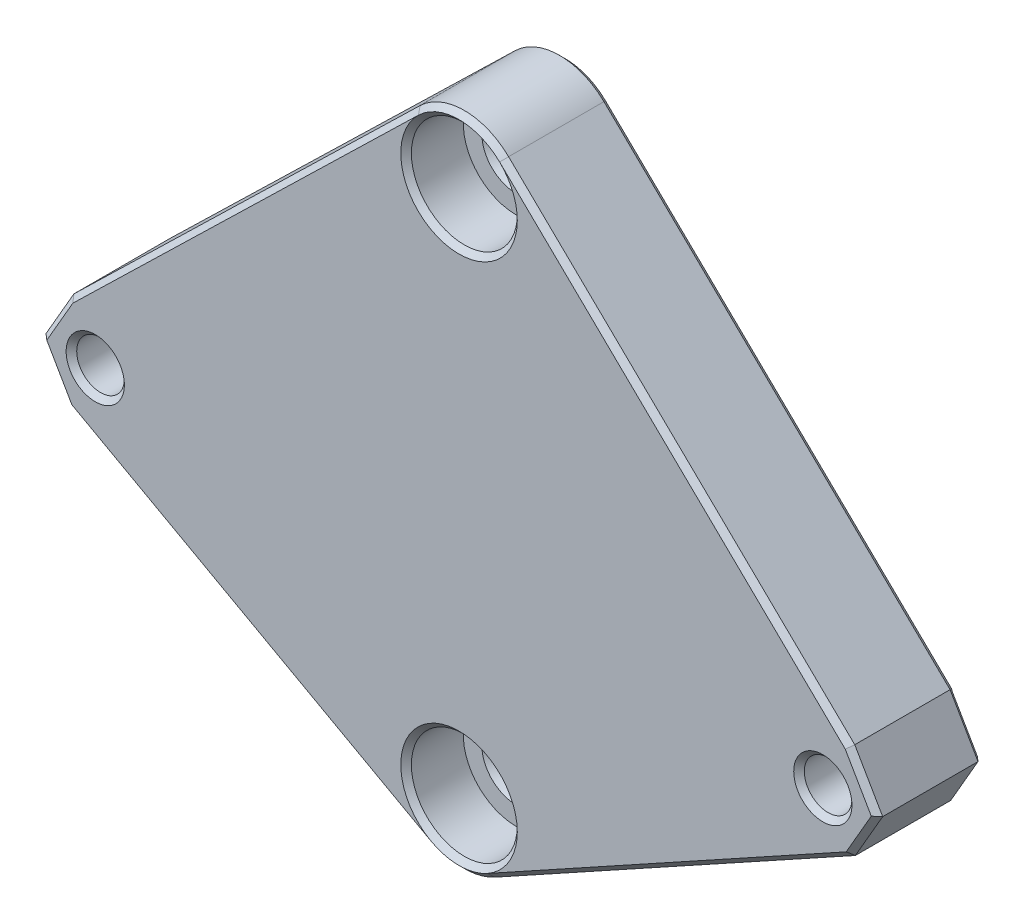
SolidWorks part; units mm, degrees
ref_plane "Top" through (0, 0, 0) normal (0, 0, 1) x (1, 0, 0)
ref_plane "Front" through (0, 0, 0) normal (0, 1, 0) x (1, 0, 0)
ref_plane "Right" through (0, 0, 0) normal (1, 0, 0) x (0, 0, -1)
sketch "Sketch1" plane through (0, 0, 0) normal (0, 0, 1) x (1, 0, 0)
  line L1 (0, 0) -> (79, 0)
  line L2 (0, 0) -> (0, 70)
  line L3 (0, 70) -> (79, 70)
  line L4 (79, 0) -> (79, 70)
  dimension "D1" = 79
  dimension "D2" = 70
extrude "Boss-Extrude1" add sketch "Sketch1" along normal blind 10
sketch "Sketch4" plane through (0, 0, 10) normal (0, 0, 1) x (1, 0, 0)
  line L0 (5.15, 28) -> (73.85, 28)
  line L2 (79, 0) -> (79, 70) construction
  line L5 (79, 70) -> (0, 70) construction
  point P2 (39.5, 28)
  dimension "D1" = 68.7
  dimension "D2" = 39.5
  dimension "D3" = 42
hole_wizard "M4 Clearance Hole1" positions "Sketch5" profile "Sketch6" hole size "M4" standard "DIN" end condition through all
sketch "Sketch5" plane through (0, 0, 10) normal (0, 0, 1) x (1, 0, 0)
  point P0 (5.15, 28)
  point P3 (73.85, 28)
sketch "Sketch6" plane through (5.15, 28, 10) normal (1, 0, 0) x (0, -1, 0)
  line L0 (0, 0) -> (0, 10)
  line L1 (0, 10) -> (2.25, 10)
  line L2 (2.25, 10) -> (2.25, 0)
  line L5 (2.25, 0) -> (0, 0)
  line L11 (0, -6.35) -> (0, 107.95) construction
  dimension "Thru Hole Dia." = 4.5
  dimension "Thru Hole Depth" = 10
sketch "Sketch11" plane through (0, 0, 0) normal (0, 0, -1) x (-1, 0, 0)
  line L0 (-79, 70) -> (0, 70) construction
  line L1 (-69.6353, 28) -> (-71.7427, 31.65)
  line L2 (-71.7427, 31.65) -> (-75.9573, 31.65)
  line L3 (-75.9573, 31.65) -> (-78.0647, 28)
  line L4 (-78.0647, 28) -> (-75.9573, 24.35)
  line L5 (-75.9573, 24.35) -> (-71.7427, 24.35)
  line L6 (-71.7427, 24.35) -> (-69.6353, 28)
  line L7 (-9.3647, 28) -> (-7.2573, 24.35)
  line L8 (-7.2573, 24.35) -> (-3.0427, 24.35)
  line L9 (-3.0427, 24.35) -> (-0.9353, 28)
  line L10 (-0.9353, 28) -> (-3.0427, 31.65)
  line L11 (-3.0427, 31.65) -> (-7.2573, 31.65)
  line L12 (-7.2573, 31.65) -> (-9.3647, 28)
  circle A0 centre (-73.85, 28) radius 3.65 construction
  circle A1 centre (-5.15, 28) radius 3.65 construction
  dimension "D1" = 7.3
  dimension "D2" = 7.3
extrude "Cut-Extrude3" cut sketch "Sketch11" against normal blind 3.5
sketch "Sketch12" plane through (0, 0, 10) normal (0, 0, -1) x (-1, 0, 0)
  line L0 (-39.5, 60) -> (-39.5, 10)
  line L1 (-79, 0) -> (-79, 70) construction
  line L2 (0, 0) -> (-79, 0) construction
  dimension "D1" = 39.5
  dimension "D2" = 50
  dimension "D3" = 10
hole_wizard "CBORE for M5 Socket Head Cap Screw1" positions "Sketch15" profile "Sketch16" counterbore size "M5" standard "DIN" end condition through all
sketch "Sketch15" plane through (0, 0, 10) normal (0, 0, 1) x (1, 0, 0)
  point P0 (39.5, 60)
  point P3 (39.5, 10)
sketch "Sketch16" plane through (39.5, 60, 10) normal (1, 0, 0) x (0, -1, 0)
  line L0 (0, 0) -> (0, 10)
  line L1 (0, 10) -> (2.75, 10)
  line L3 (2.75, 10) -> (2.75, 5.4)
  line L4 (2.75, 5.4) -> (5, 5.4)
  line L5 (5, 5.4) -> (5, 0)
  line L7 (5, 0) -> (0, 0)
  line L11 (0, -6.35) -> (0, 107.95) construction
  dimension "Thru Hole Dia." = 5.5
  dimension "Thru Hole Depth" = 10
  dimension "C'Bore Dia." = 10
  dimension "C'Bore Depth" = 5.4
sketch "Sketch17" plane through (0, 0, 0) normal (0, 0, -1) x (-1, 0, 0)
  line L0 (-76.3644, 32.565) -> (-43.68, 64.3044)
  line L2 (-35.32, 64.3044) -> (-2.6356, 32.565)
  line L4 (-76.4203, 23.5319) -> (-42.4002, 4.7475)
  line L5 (-36.5998, 4.7475) -> (-2.5797, 23.5319)
  line L14 (-2.5797, 23.5319) -> (0, 28)
  line L15 (0, 70) -> (0, 0) construction
  line L16 (0, 28) -> (-2.6356, 32.565)
  line L17 (-0.9353, 28) -> (-3.0427, 31.65) construction
  line L18 (-3.0427, 24.35) -> (-0.9353, 28) construction
  line L20 (-76.3644, 32.565) -> (-79, 28)
  line L21 (-79, 0) -> (-79, 70) construction
  line L22 (-79, 28) -> (-76.4203, 23.5319)
  line L23 (-78.0647, 28) -> (-75.9573, 24.35) construction
  line L24 (-75.9573, 31.65) -> (-78.0647, 28) construction
  line L25 (-125.188, 28) -> (-105.4971, -6.1057)
  line L26 (-105.4971, -6.1057) -> (-61.7349, -30.2692)
  line L27 (-17.2651, -30.2692) -> (26.4971, -6.1057)
  line L28 (26.4971, -6.1057) -> (46.188, 28)
  line L29 (46.188, 28) -> (29.223, 57.3843)
  line L30 (-7.4537, 93.0005) -> (29.223, 57.3843)
  line L31 (-108.223, 57.3843) -> (-71.5463, 93.0005)
  line L32 (-108.223, 57.3843) -> (-125.188, 28)
  arc A0 (-43.68, 64.3044) -> (-35.32, 64.3044) centre (-39.5, 60) cw
  arc A1 (-42.4002, 4.7475) -> (-36.5998, 4.7475) centre (-39.5, 10) ccw
  arc A4 (-61.7349, -30.2692) -> (-17.2651, -30.2692) centre (-39.5, 10) ccw
  arc A5 (-71.5463, 93.0005) -> (-7.4537, 93.0005) centre (-39.5, 60) cw
  point P24 (0, 0)
  dimension "D2" = 6
  dimension "D4" = 6
  dimension "D1" = 0.94
  dimension "D3" = 0.94
  dimension "D5" = 0.94
  dimension "D6" = 0.94
  dimension "D7" = 40
extrude "Cut-Extrude4" cut sketch "Sketch17" against normal blind 10
chamfer "Chamfer1" distance 0.5 angle 45 38 edges at (77.7102, 25.7659, 10) (59.4103, 14.1397, 10) (39.5, 4, 10) (19.5897, 14.1397, 10) (1.2898, 25.7659, 10) (1.3178, 30.2825, 10) (18.9778, 48.4347, 10) (39.5, 66, 10) (60.0222, 48.4347, 10) (77.6822, 30.2825, 10) (76.1, 28, 10) (7.4, 28, 10) (44.5, 10, 10) (44.5, 60, 10) (39.5, 66, 0) (18.9778, 48.4347, 0) (1.3178, 30.2825, 0) (1.2898, 25.7659, 0) (19.5897, 14.1397, 0) (39.5, 4, 0) (59.4103, 14.1397, 0) (77.7102, 25.7659, 0) (77.6822, 30.2825, 0) (60.0222, 48.4347, 0) (8.311, 26.175, 0) (5.15, 24.35, 0) (1.989, 26.175, 0) (1.989, 29.825, 0) (5.15, 31.65, 0) (8.311, 29.825, 0) (70.689, 29.825, 0) (73.85, 31.65, 0) (77.011, 29.825, 0) (77.011, 26.175, 0) (73.85, 24.35, 0) (70.689, 26.175, 0) (42.25, 10, 0) (42.25, 60, 0)
chamfer "Chamfer2" distance 0.5 angle 45 2 edges at (42.25, 10, 4.6) (42.25, 60, 4.6)
